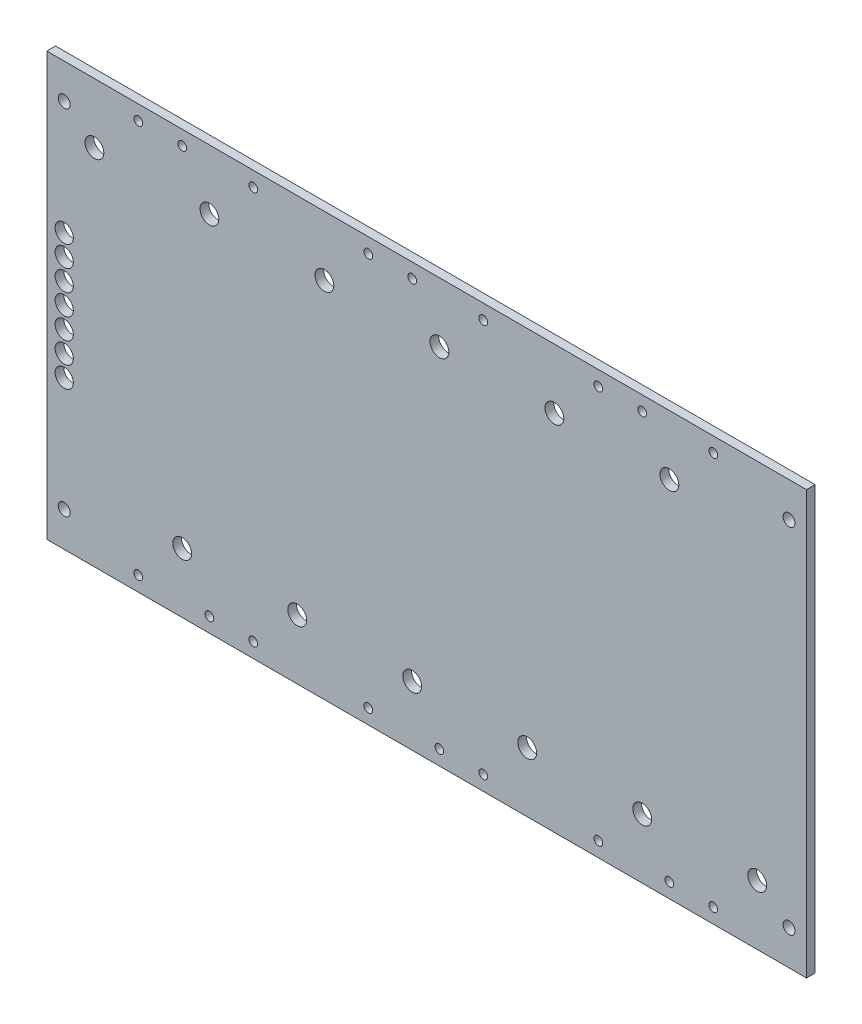
SolidWorks part; units mm, degrees
ref_plane "Front Plane" through (0, 0, 0) normal (0, 0, 1) x (1, 0, 0)
ref_plane "Top Plane" through (0, 0, 0) normal (0, 1, 0) x (1, 0, 0)
ref_plane "Right Plane" through (0, 0, 0) normal (1, 0, 0) x (0, 0, -1)
sketch "Sketch1" plane through (0, 0, 0) normal (0, 0, 1) x (1, 0, 0)
  line L0 (20.955, 77.0636) -> (20.955, 0) construction
  line L1 (0, 0) -> (132.08, 0)
  line L2 (0, 0) -> (0, 77.0636) construction
  line L3 (0, 77.0636) -> (132.08, 77.0636)
  line L4 (132.08, 77.0636) -> (132.08, 0)
  line L5 (20.6502, 77.0636) -> (20.6502, 0) construction
  line L6 (10.3251, 74.3712) -> (0, 74.3712) construction
  line L7 (10.3251, 74.3712) -> (20.6502, 74.3712) construction
  line L8 (10.3251, 2.6924) -> (10.3251, 0) construction
  line L9 (10.3251, 74.3712) -> (10.3251, 77.0636) construction
  line L10 (18.3261, 66.1543) -> (20.6502, 66.1543) construction
  line L11 (2.3241, 66.1543) -> (0, 66.1543) construction
  line L12 (18.3261, 10.9093) -> (20.6502, 10.9093) construction
  line L13 (41.6052, 77.0636) -> (41.6052, 0) construction
  line L14 (18.3261, 66.1543) -> (18.3261, 77.0636) construction
  line L15 (18.3261, 10.9093) -> (18.3261, 0) construction
  line L16 (20.955, 66.1543) -> (23.2791, 66.1543) construction
  line L17 (41.6052, 66.1543) -> (36.2579, 66.1543) construction
  line L18 (41.6052, 74.3712) -> (20.955, 74.3712) construction
  line L19 (31.2801, 74.3712) -> (31.2801, 77.0636) construction
  line L20 (31.2801, 0) -> (31.2801, 2.6924) construction
  line L21 (0, 77.0636) -> (-6.35, 77.0636)
  line L22 (-6.35, 77.0636) -> (-6.35, 0)
  line L23 (-6.35, 0) -> (0, 0)
  line L24 (41.6052, 10.9093) -> (39.2811, 10.9093) construction
  line L25 (41.6052, 2.6924) -> (31.2801, 2.6924) construction
  line L26 (83.5152, 77.0636) -> (83.5152, 0) construction
  line L27 (-3.175, 70.7136) -> (-3.175, 77.0636) construction
  line L28 (-3.175, 6.35) -> (-3.175, 0) construction
  line L29 (62.865, 77.0636) -> (62.865, 0) construction
  line L30 (62.5602, 77.0636) -> (62.5602, 0) construction
  line L31 (41.91, 0) -> (41.91, 77.0636) construction
  line L32 (125.4252, 77.0636) -> (125.4252, 0) construction
  line L33 (104.775, 77.0636) -> (104.775, 0) construction
  line L34 (104.4702, 77.0636) -> (104.4702, 0) construction
  line L35 (83.82, 0) -> (83.82, 77.0636) construction
  line L36 (41.6052, 77.0636) -> (83.5152, 77.0636) construction
  line L37 (128.905, 77.0636) -> (128.905, 70.7136) construction
  line L38 (128.905, 0) -> (128.905, 6.35) construction
  line L39 (20.955, 2.6924) -> (23.2791, 2.6924) construction
  line L40 (23.2791, 2.6924) -> (65.1891, 2.6924) construction
  line L41 (94.1451, 74.3712) -> (115.1001, 74.3712) construction
  line L42 (-3.175, 38.5318) -> (-6.35, 38.5318) construction
  line L43 (-3.175, 38.5318) -> (-3.175, 42.3418) construction
  circle A0 centre (10.3251, 74.3712) radius 0.7937
  circle A1 centre (10.3251, 2.6924) radius 0.7937
  circle A2 centre (2.3241, 66.1543) radius 1.7145
  circle A3 centre (18.3261, 74.4347) radius 0.7937
  circle A4 centre (18.3261, 10.9093) radius 1.7145
  circle A5 centre (23.2791, 66.1543) radius 1.7145
  circle A6 centre (31.2801, 74.3712) radius 0.7937
  circle A7 centre (31.2801, 2.6924) radius 0.7937
  circle A8 centre (39.2811, 10.9093) radius 1.7145
  circle A9 centre (31.2801, 2.6924) radius 0.7937
  circle A10 centre (65.1891, 66.1543) radius 1.7145
  circle A11 centre (73.1901, 2.6924) radius 0.7937
  circle A12 centre (73.1901, 2.6924) radius 0.7937
  circle A13 centre (81.1911, 10.9093) radius 1.7145
  circle A14 centre (73.1901, 74.3712) radius 0.7937
  circle A15 centre (65.1891, 2.6924) radius 0.7937
  circle A16 centre (52.2351, 74.3712) radius 0.7937
  circle A17 centre (44.2341, 66.1543) radius 1.7145
  circle A18 centre (-3.175, 70.7136) radius 1.0922
  circle A19 centre (-3.175, 6.35) radius 1.0922
  circle A20 centre (60.2361, 10.9093) radius 1.7145
  circle A21 centre (52.2351, 2.6924) radius 0.7937
  circle A22 centre (107.0991, 66.1543) radius 1.7145
  circle A23 centre (115.1001, 2.6924) radius 0.7937
  circle A24 centre (115.1001, 2.6924) radius 0.7937
  circle A25 centre (123.1011, 10.9093) radius 1.7145
  circle A26 centre (60.2361, 74.4347) radius 0.7937
  circle A27 centre (102.1461, 74.4347) radius 0.7937
  circle A28 centre (94.1451, 74.3712) radius 0.7937
  circle A29 centre (86.1441, 66.1543) radius 1.7145
  circle A30 centre (102.1461, 10.9093) radius 1.7145
  circle A31 centre (94.1451, 2.6924) radius 0.7937
  circle A32 centre (128.905, 70.7136) radius 1.0922
  circle A33 centre (128.905, 6.35) radius 1.0922
  circle A34 centre (23.2791, 2.6924) radius 0.7937
  circle A35 centre (60.2361, 74.4347) radius 0.7937 [skipped]
  circle A36 centre (115.1001, 74.3712) radius 0.7937 [skipped]
  circle A37 centre (107.0991, 2.6924) radius 0.7937
  circle A38 centre (102.1461, 74.4347) radius 0.7937
  circle A39 centre (115.1001, 74.3712) radius 0.7937
  circle A40 centre (-3.175, 38.5318) radius 1.6593
  circle A41 centre (-3.175, 42.3418) radius 1.6593
  circle A42 centre (-3.175, 46.1518) radius 1.6593
  circle A43 centre (-3.175, 49.9618) radius 1.6593
  circle A44 centre (-3.175, 38.5318) radius 1.6593
  circle A45 centre (-3.175, 42.3418) radius 1.6593
  circle A46 centre (-3.175, 46.1518) radius 1.6593
  circle A47 centre (-3.175, 34.7218) radius 1.6593
  circle A48 centre (-3.175, 38.5318) radius 1.6593
  circle A49 centre (-3.175, 42.3418) radius 1.6593
  circle A50 centre (-3.175, 30.9118) radius 1.6593
  circle A51 centre (-3.175, 34.7218) radius 1.6593
  circle A52 centre (-3.175, 38.5318) radius 1.6593
  circle A53 centre (-3.175, 34.7218) radius 1.6593
  circle A54 centre (-3.175, 30.9118) radius 1.6593
  circle A55 centre (-3.175, 27.1018) radius 1.6593
  dimension "D6" = 1.5875
  dimension "D7" = 3.429
  dimension "D13" = 2.1844
  dimension "D15" = 20.6502
  dimension "D11" = 1.5875
  dimension "D16" = 3
  dimension "D18" = 41.91
  dimension "D24" = 3.3186
  dimension "D1" = 77.0636
  dimension "D2" = 132.08
  dimension "D3" = 20.6502
  dimension "D4" = 20.955
  dimension "D5" = 71.6788
  dimension "D8" = 16.002
  dimension "D9" = 55.245
  dimension "D10" = 8.2804
  dimension "D12" = 6.35
  dimension "D14" = 6.35
  dimension "D17" = 3
  dimension "D19" = 71.6788
  dimension "D20" = 3.175
  dimension "D21" = 41.91
  dimension "D23" = 20.955
  dimension "D27" = 3.81
  dimension "D22" = 2
  dimension "D25" = 4
  dimension "D26" = 4
extrude "Boss-Extrude1" add sketch "Sketch1" along normal blind 1.5875 contours L1 L4 L3 L2 A4 A2 A1 A0 | L22 L23 L2 L21 A19 A18 | L4 region at (63.2499, 38.5318, 0)
